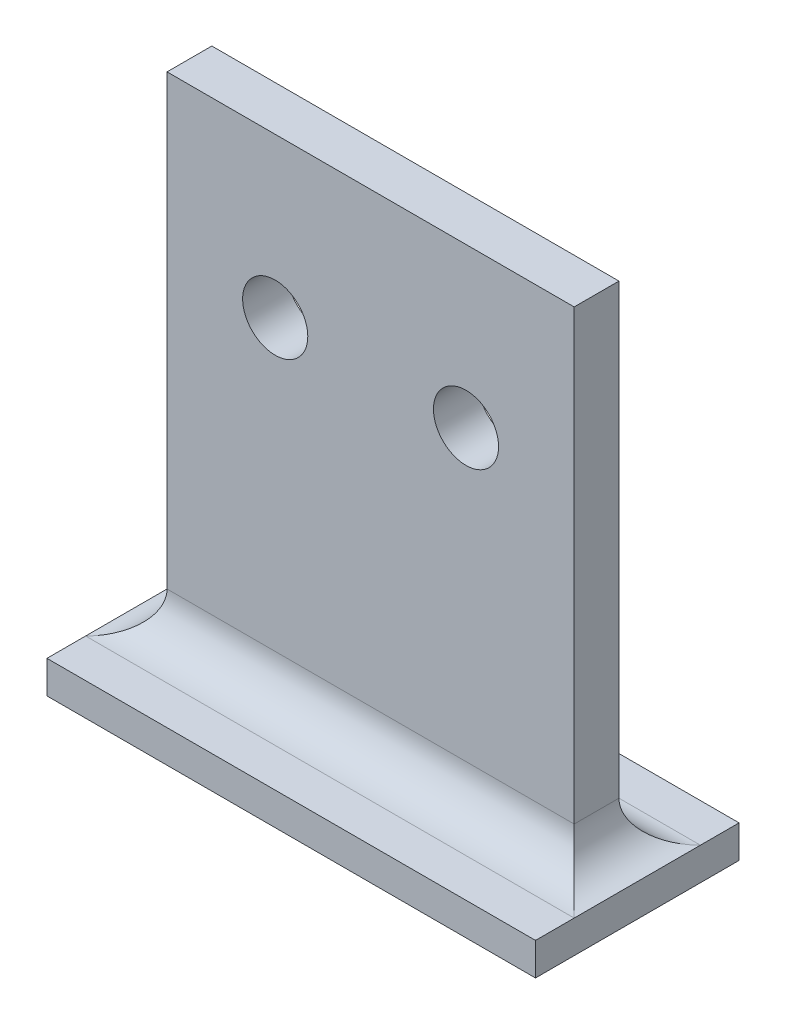
SolidWorks part; units mm, degrees
ref_plane "Front Plane" through (0, 0, 0) normal (0, 0, 1) x (1, 0, 0)
ref_plane "Top Plane" through (0, 0, 0) normal (0, 1, 0) x (1, 0, 0)
ref_plane "Right Plane" through (0, 0, 0) normal (1, 0, 0) x (0, 0, -1)
sketch "Sketch1" plane through (0, 0, 0) normal (0, 0, 1) x (1, 0, 0)
  line L1 (30, -1.1928) -> (-30, -1.1928)
  line L2 (30, -1.1928) -> (30, 2.8072)
  line L3 (30, 2.8072) -> (-30, 2.8072)
  line L4 (-30, -1.1928) -> (-30, 2.8072)
  point P0 (0, 0)
  point P6 (0, 0)
  point P7 (0, -1.1928)
  point P8 (0, 0)
  dimension "D1" = 60
  dimension "D2" = 4
extrude "Boss-Extrude1" add sketch "Sketch1" along normal blind 25
sketch "Sketch2" plane through (0, 2.8072, 0) normal (0, 1, 0) x (1, 0, 0)
  line L0 (30, -25) -> (30, 0) construction
  line L1 (-25, -9.75) -> (25, -9.75)
  line L2 (-25, -9.75) -> (-25, -15.25)
  line L3 (-25, -15.25) -> (25, -15.25)
  line L4 (25, -9.75) -> (25, -15.25)
  line L5 (-25, -9.75) -> (25, -15.25) construction
  line L6 (-25, -15.25) -> (25, -9.75) construction
  point P0 (0, -12.5)
  point P7 (30, -12.5)
  dimension "D1" = 5.5
  dimension "D2" = 50
extrude "Boss-Extrude2" add sketch "Sketch2" along normal blind 60
fillet "Fillet1" radius 5 4 edges at (0, 2.8072, 9.75) (25, 2.8072, 12.5) (-25, 2.8072, 12.5) (0, 2.8072, 15.25)
sketch "Sketch3" plane through (0, 0, 15.25) normal (0, 0, 1) x (1, 0, 0)
  line L0 (0, 65.9795) -> (0, -3.9951)
  line L1 (30, 2.8072) -> (-30, 2.8072) construction
  circle A0 centre (-11.715, 43.3072) radius 4
  circle A1 centre (11.715, 43.3072) radius 4
  dimension "D2" = 8
  dimension "D3" = 40.5
  dimension "D1" = 23.43
extrude "Cut-Extrude1" cut sketch "Sketch3" against normal blind 60 contours A0 | A1 region at (-11.715, 43.3072, 15.25) region at (11.715, 43.3072, 15.25)
